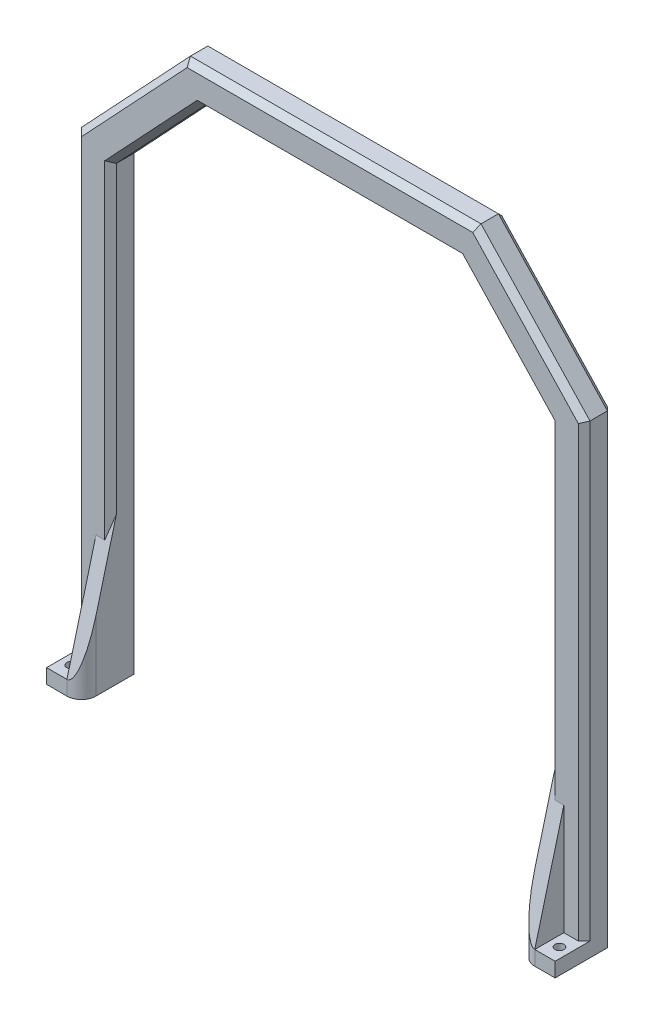
SolidWorks part; units mm, degrees
ref_plane "Front Plane" through (0, 0, 0) normal (0, 0, 1) x (1, 0, 0)
ref_plane "Top Plane" through (0, 0, 0) normal (0, 1, 0) x (1, 0, 0)
ref_plane "Right Plane" through (0, 0, 0) normal (1, 0, 0) x (0, 0, -1)
sketch "Sketch1" plane through (0, 0, 0) normal (0, 0, 1) x (1, 0, 0)
  line L0 (-87.5, -200) -> (-87.5, -40)
  line L1 (-87.5, -40) -> (-50, 0)
  line L2 (-50, 0) -> (50, 0)
  line L3 (50, 0) -> (87.5, -40)
  line L4 (87.5, -40) -> (87.5, -200)
  line L5 (-87.5, -40) -> (87.5, -40) construction
  line L6 (0, -40) -> (0, 0) construction
  line L7 (-87.5, -200) -> (87.5, -200) construction
  line L8 (-75.5, -200) -> (-75.5, -44.7454)
  line L9 (-75.5, -44.7454) -> (-44.8012, -12)
  line L10 (-44.8012, -12) -> (44.8012, -12)
  line L11 (44.8012, -12) -> (75.5, -44.7454)
  line L12 (75.5, -44.7454) -> (75.5, -200)
  line L13 (-87.5, -200) -> (-75.5, -200)
  line L14 (75.5, -200) -> (87.5, -200)
  dimension "D1" = 100
  dimension "D2" = 175
  dimension "D3" = 40
  dimension "D4" = 160
  dimension "D5" = 12
extrude "Boss-Extrude1" add sketch "Sketch1" along normal blind 5 and the other way blind 5
sketch "Sketch2" plane through (0, 0, 5) normal (0, 0, 1) x (1, 0, 0)
  line L0 (-75.5, -200) -> (-75.5, -44.7454) construction
  line L1 (-87.5, -200) -> (-75.5, -200)
  line L2 (-87.5, -200) -> (-87.5, -195)
  line L3 (-87.5, -195) -> (-80.5, -195)
  line L4 (-75.5, -200) -> (-75.5, -197)
  line L5 (-87.5, -40) -> (-87.5, -200) construction
  line L7 (-80.5, -195) -> (-80.5, -157)
  line L8 (-80.5, -157) -> (-75.5, -157)
  line L9 (-75.5, -197) -> (-75.5, -157)
  dimension "D1" = 5
  dimension "D2" = 40
  dimension "D3" = 7
extrude "Boss-Extrude2" add sketch "Sketch2" along normal blind 10
sketch "Sketch3" plane through (-80.5, 0, 0) normal (-1, 0, 0) x (0, 0, 1)
  line L0 (5, -157) -> (15, -195)
  line L1 (15, -195) -> (15, -157)
  line L2 (15, -157) -> (5, -157)
extrude "Cut-Extrude1" cut sketch "Sketch3" against normal through all
sketch "Sketch4" plane through (0, -195, 0) normal (0, 1, 0) x (1, 0, 0)
  line L0 (-87.5, -15) -> (-87.5, -5) construction
  line L1 (-80.5, -15) -> (-87.5, -15) construction
  circle A0 centre (-84, -10) radius 1.5537
  dimension "D1" = 3.5
  dimension "D2" = 5
extrude "Cut-Extrude2" cut sketch "Sketch4" against normal through all
mirror "Mirror1" about plane through (0, 0, 0) normal (1, 0, 0) of "Cut-Extrude1", "Boss-Extrude2", "Cut-Extrude2"
chamfer "Chamfer1" distance 2 angle 45 12 edges at (-75.5, -122.3727, -5) (-60.1506, -28.3727, -5) (0, -12, -5) (60.1506, -28.3727, -5) (75.5, -122.3727, -5) (81.5, -200, -5) (87.5, -120, -5) (68.75, -20, -5) (0, 0, -5) (-68.75, -20, -5) (-87.5, -120, -5) (-81.5, -200, -5)
chamfer "Chamfer2" distance 2 angle 45 10 edges at (75.5, -100.8727, 5) (60.1506, -28.3727, 5) (0, -12, 5) (-75.5, -100.8727, 5) (-60.1506, -28.3727, 5) (87.5, -117.5, 5) (68.75, -20, 5) (0, 0, 5) (-68.75, -20, 5) (-87.5, -117.5, 5)
fillet "Fillet1" radius 5 2 edges at (75.5, -197.5, 15) (-75.5, -197.5, 15)
